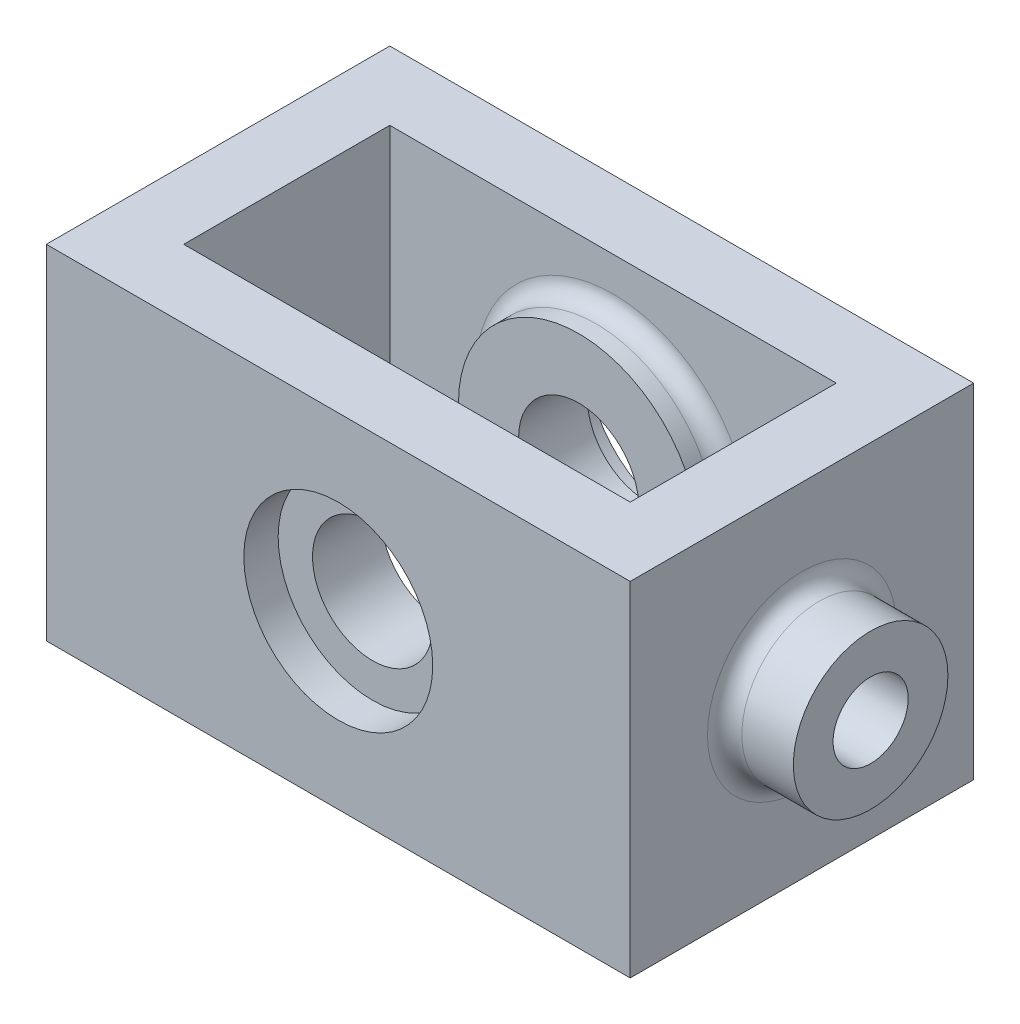
SolidWorks part; units mm, degrees
ref_plane "Front Plane" through (0, 0, 0) normal (0, 0, 1) x (1, 0, 0)
ref_plane "Top Plane" through (0, 0, 0) normal (0, 1, 0) x (1, 0, 0)
ref_plane "Right Plane" through (0, 0, 0) normal (1, 0, 0) x (0, 0, -1)
sketch "Sketch1" plane through (0, 0, 0) normal (0, 0, 1) x (1, 0, 0)
  line L1 (-43.18, 25.4) -> (43.18, 25.4)
  line L2 (-43.18, 25.4) -> (-43.18, -25.4)
  line L3 (-43.18, -25.4) -> (43.18, -25.4)
  line L4 (43.18, 25.4) -> (43.18, -25.4)
  line L5 (-43.18, 25.4) -> (43.18, -25.4) construction
  line L6 (-43.18, -25.4) -> (43.18, 25.4) construction
  circle A0 centre (0, 0) radius 8.89
  circle A1 centre (0, 0) radius 13.97
  point P0 (0, 0)
  dimension "D3" = 17.78
  dimension "D4" = 27.94
  dimension "D1" = 50.8
  dimension "D2" = 86.36
extrude "Boss-Extrude2" add sketch "Sketch1" along normal mid plane 50.8 contours L4 L1 L2 L3 A1 | A1 | A0 region at (0, 24.3981, 0)
extrude "Cut-Extrude2" cut sketch "Sketch1<3>" against normal blind 5.08 from surface contours A1 A0 region at (-13.5749, 0, 0) starting at face at (0, 0, 25.4)
sketch "Sketch1<3>" plane through (0, 0, 0) normal (0, 0, 1) x (1, 0, 0) same geometry as "Sketch1"
extrude "Cut-Extrude4" cut sketch "Sketch1<4>" along normal blind 5.08 from surface contours A1 A0 region at (-13.5749, 0, 0) starting at face at (0, 0, -25.4)
sketch "Sketch1<4>" plane through (0, 0, 0) normal (0, 0, 1) x (1, 0, 0) same geometry as "Sketch1"
sketch "Sketch3" plane through (43.18, 0, 0) normal (1, 0, 0) x (0, 0, -1)
  circle A0 centre (0, 0) radius 11.43
  circle A1 centre (0, 0) radius 5.5562
  dimension "D1" = 22.86
  dimension "D2" = 11.1125
extrude "Boss-Extrude3" add sketch "Sketch3" along normal blind 10.16
mirror "Mirror1" about plane through (0, 0, 0) normal (1, 0, 0) of "Boss-Extrude3"
extrude "Cut-Extrude5" cut sketch "Sketch3<2>" against normal through all contours A1 region at (43.18, 0, 0)
sketch "Sketch3<2>" plane through (43.18, 0, 0) normal (1, 0, 0) x (0, 0, -1) same geometry as "Sketch3"
sketch "Sketch4" plane through (0, 25.4, 0) normal (0, 1, 0) x (1, 0, 0)
  line L0 (-43.18, -25.4) -> (43.18, -25.4) construction
  line L1 (-33.02, 15.24) -> (33.02, 15.24)
  line L2 (-33.02, 15.24) -> (-33.02, -15.24)
  line L3 (-33.02, -15.24) -> (33.02, -15.24)
  line L4 (33.02, 15.24) -> (33.02, -15.24)
  line L5 (-33.02, 15.24) -> (33.02, -15.24) construction
  line L6 (-33.02, -15.24) -> (33.02, 15.24) construction
  line L7 (43.18, -25.4) -> (43.18, 25.4) construction
  point P0 (0, 0)
  dimension "D1" = 10.16
  dimension "D2" = 10.16
extrude "Cut-Extrude6" cut sketch "Sketch4" against normal through all
sketch "Sketch5" plane through (0, 0, 0) normal (0, 0, 1) x (1, 0, 0)
  circle A0 centre (0, 0) radius 17.78
  circle A1 centre (0, 0) radius 8.89
  dimension "D1" = 35.56
extrude "Boss-Extrude4" add sketch "Sketch5" against normal blind 5.08 from surface starting at face at (8.89, 0, 15.24)
extrude "Boss-Extrude5" add sketch "Sketch5<2>" along normal blind 5.08 from surface starting at face at (-8.89, 0, -15.24)
sketch "Sketch5<2>" plane through (0, 0, 0) normal (0, 0, 1) x (1, 0, 0) same geometry as "Sketch5"
fillet "Fillet1" radius 2.54 2 edges at (17.78, 0, 15.24) (-17.78, 0, -15.24)
fillet "Fillet2" radius 2.54 2 edges at (-43.18, 0, -11.43) (43.18, 0, -11.43)
